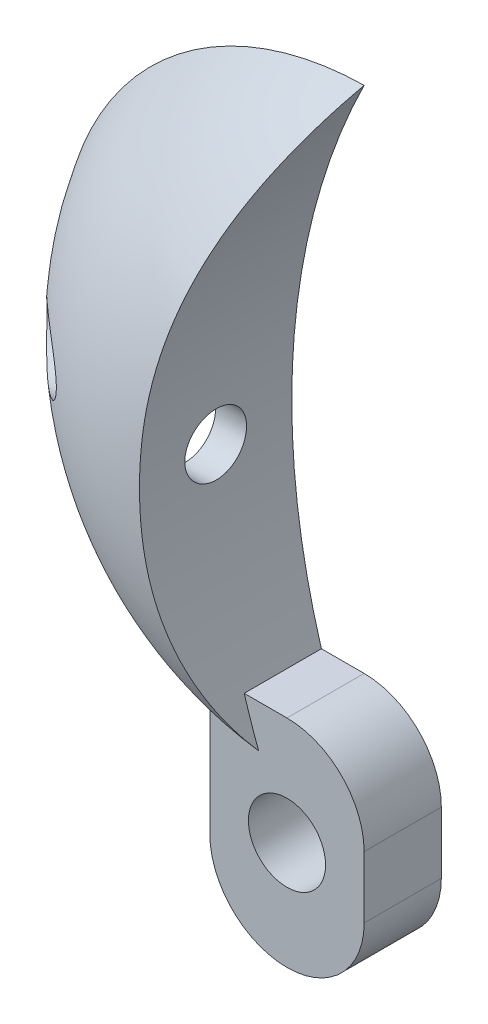
SolidWorks part; units mm, degrees
ref_plane "前视基准面" through (0, 0, 0) normal (0, 0, 1) x (1, 0, 0)
ref_plane "上视基准面" through (0, 0, 0) normal (0, 1, 0) x (1, 0, 0)
ref_plane "右视基准面" through (0, 0, 0) normal (1, 0, 0) x (0, 0, -1)
other "Configuration Table"
sketch "Sketch1" plane through (0, 0, 0) normal (0, 0, 1) x (1, 0, 0)
  line L0 (0, 0) -> (20, 0) construction
  line L1 (0, 0) -> (12.2305, 0) construction
  line L2 (-0.1563, 9.9988) -> (-0.1563, -9.9988) construction
  arc A0 (-0.1563, 9.9988) -> (-0.1563, -9.9988) centre (0, 0) ccw
  arc A1 (-0.1563, 9.9988) -> (-0.1563, -9.9988) centre (20, 0) ccw
  dimension "D1" = 20
  dimension "D4" = 45
  dimension "D2" = 0
  dimension "D3" = 20
extrude "Boss-Extrude1" add sketch "Sketch1" along normal blind 5
fillet "Fillet1" radius 10 1 edges at (-10, 0, 5)
shell "Shell1" thickness 1 removed face at (-6.25, 0, 0)
sketch "Sketch4" plane through (0, 0, 0) normal (1, 0, 0) x (0, 0, -1)
  line L0 (0, 0) -> (-4.9325, 0) construction
  line L1 (0, -9.9988) -> (0, 9.9988) construction
  line L2 (-4.9325, 0) -> (-2.4662, 0) construction
  circle A0 centre (-2.4662, 0) radius 1
  spline S0 degree 3 poles (0, 9.9988) (-0.846, 9.5065) (-1.5866, 8.9036) (-2.3941, 8.0113) (-2.5501, 7.8251) (-2.8455, 7.4437) (-2.9854, 7.2482) (-3.3828, 6.647) (-3.6179, 6.227) (-4.0306, 5.3482) (-4.2087, 4.8862) (-4.4998, 3.9487) (-4.614, 3.4709) (-4.787, 2.4985) (-4.8455, 2.0027) (-4.9179, 1.0012) (-4.9325, 0.4994) (-4.9324, -0.5029) (-4.9177, -1.0039) (-4.8452, -2.0055) (-4.7869, -2.4989) (-4.6144, -3.4688) (-4.5006, -3.9453) (-4.2107, -4.8804) (-4.0328, -5.3429) (-3.4133, -6.6638) (-2.8893, -7.4617) (-2.082, -8.3569) (-1.9124, -8.5309) (-1.5625, -8.8631) (-1.3816, -9.022) (-0.821, -9.4773) (-0.4233, -9.7524) (0, -9.9988) knots 0 0 0 0 0.125 0.125 0.15625 0.15625 0.1875 0.1875 0.25 0.25 0.3125 0.3125 0.375 0.375 0.4375 0.4375 0.5 0.5 0.5625 0.5625 0.625 0.625 0.6875 0.6875 0.75 0.75 0.875 0.875 0.90625 0.90625 0.9375 0.9375 1 1 1 1 construction
  dimension "D1" = 2
extrude "Cut-Extrude1" cut sketch "Sketch4" against normal through all
sketch "Sketch5" plane through (0, 0, 0) normal (0, 0, 1) x (1, 0, 0)
  line L1 (-2.6563, -13.4988) -> (2.3437, -13.4988)
  line L2 (-2.6563, -13.4988) -> (-2.6563, -6.4988)
  line L3 (-2.6563, -6.4988) -> (2.3437, -6.4988)
  line L4 (2.3437, -13.4988) -> (2.3437, -6.4988)
  line L5 (-2.6563, -13.4988) -> (2.3437, -6.4988) construction
  line L6 (-2.6563, -6.4988) -> (2.3437, -13.4988) construction
  point P0 (-0.1563, -9.9988)
  dimension "D1" = 5
  dimension "D2" = 7
extrude "Boss-Extrude2" add sketch "Sketch5" along normal blind 2.5
sketch "Sketch7" plane through (0, 0, 2.5) normal (0, 0, 1) x (1, 0, 0)
  line L0 (2.3437, -6.4988) -> (2.3437, -13.4988) construction
  line L1 (2.3437, -13.4988) -> (2.3437, -9.9988) construction
  line L2 (2.3437, -9.9988) -> (-2.6563, -9.9988) construction
  line L3 (-2.6563, -7.4975) -> (-2.6563, -13.4988) construction
  circle A0 centre (-0.1563, -9.9988) radius 1.25
  point P8 (-0.1563, -9.9988)
  dimension "D1" = 2.5
extrude "Cut-Extrude3" cut sketch "Sketch7" against normal through all
fillet "Fillet4" radius 2.5 3 edges at (-2.6563, -13.4988, 1.25) (2.3437, -13.4988, 1.25) (2.3437, -6.4988, 1.25)
